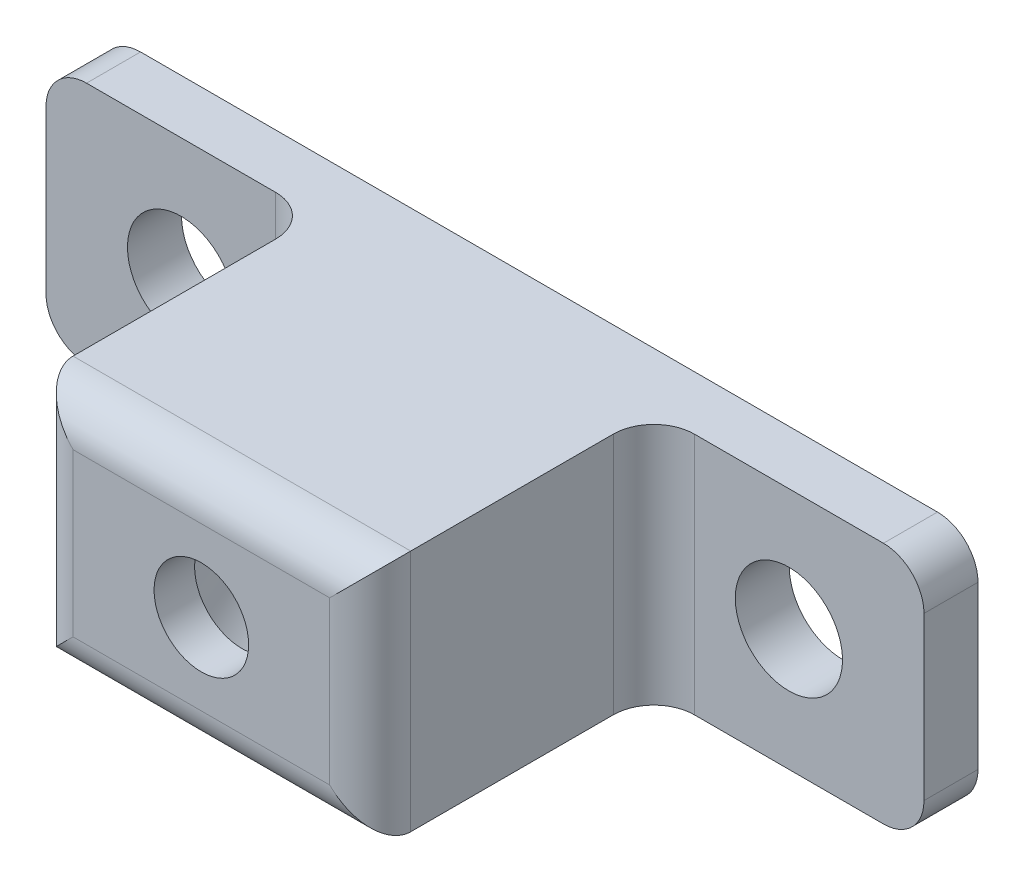
SolidWorks part; units mm, degrees
ref_plane "Front Plane" through (0, 0, 0) normal (0, 0, 1) x (1, 0, 0)
ref_plane "Top Plane" through (0, 0, 0) normal (0, 1, 0) x (1, 0, 0)
ref_plane "Right Plane" through (0, 0, 0) normal (1, 0, 0) x (0, 0, -1)
sketch "Sketch1" plane through (0, 0, 0) normal (0, 0, 1) x (1, 0, 0)
  line L0 (25, 18) -> (0, 0) construction
  line L1 (0, 0) -> (25, 0)
  line L2 (0, 0) -> (0, 18)
  line L3 (0, 18) -> (25, 18)
  line L4 (25, 0) -> (25, 18)
  line L5 (0, 18) -> (25, 0) construction
  circle A0 centre (12.5, 9) radius 3.5
  dimension "D1" = 7
  dimension "D2" = 25
  dimension "D3" = 18
extrude "Boss-Extrude1" add sketch "Sketch1" along normal blind 25
sketch "Sketch2" plane through (0, 0, 0) normal (0, 0, -1) x (-1, 0, 0)
  line L0 (20, 0) -> (0, 18) construction
  line L1 (0, 18) -> (20, 18)
  line L2 (0, 18) -> (0, 0)
  line L3 (0, 0) -> (20, 0)
  line L4 (20, 18) -> (20, 0)
  line L5 (20, 18) -> (0, 0) construction
  line L6 (-25, 0) -> (-45, 18) construction
  line L7 (-25, 0) -> (-45, 0)
  line L8 (-25, 0) -> (-25, 18)
  line L9 (-25, 18) -> (-45, 18)
  line L10 (-45, 0) -> (-45, 18)
  line L12 (-25, 18) -> (-45, 0) construction
  circle A0 centre (10, 9) radius 3.9688
  circle A1 centre (-35, 9) radius 3.9688
  dimension "D1" = 7.9375
  dimension "D2" = 20
extrude "Boss-Extrude2" add sketch "Sketch2" against normal blind 4
fillet "Fillet2" radius 3 6 edges at (-20, 0, 2) (-20, 18, 2) (45, 0, 2) (45, 18, 2)
fillet "Fillet4" radius 3 4 edges at (12.5, 0, 25) (12.5, 18, 25) (0, 9, 25) (25, 9, 25)
sketch "Sketch3" plane through (0, 0, 0) normal (0, 0, -1) x (-1, 0, 0)
  circle A0 centre (-12.5, 9) radius 4.65
extrude "Cut-Extrude1" cut sketch "Sketch3" against normal offset from surface (22 mm away) 3 up to face at (12.5, 9, 25)
sketch "Sketch5" plane through (0, 0, 0) normal (0, 0, -1) x (-1, 0, 0)
  line L1 (-3, 3) -> (-22, 3)
  line L5 (17, 0) -> (-42, 0) construction
  line L6 (-42, 18) -> (17, 18) construction
  line L8 (-3, 3) -> (-3, 15)
  line L9 (-3, 15) -> (-22, 15)
  line L10 (-22, 3) -> (-22, 15)
  line L11 (-25, 18) -> (-25, 0) construction
  line L12 (0, 18) -> (0, 0) construction
  dimension "D2" = 3
  dimension "D3" = 3
  dimension "D4" = 3
  dimension "D5" = 3
extrude "Cut-Extrude2" cut sketch "Sketch5" against normal offset from surface (22 mm away) 3 up to face at (12.5, 9, 25)
chamfer "Chamfer1" distance 1.25 angle 75 2 edges at (12.5, 15, 22) (12.5, 3, 22) first distance on face at (9, 9, 22)
chamfer "Chamfer2" distance 4.5 angle 60 2 edges at (22, 9, 22) (3, 9, 22) first distance on face at (9, 9, 22)
fillet "Fillet5" radius 5.54 4 edges at (6.1533, 3.625, 19.6675) (18.8467, 3.625, 19.6675) (18.8467, 14.375, 19.6675) (6.1533, 14.375, 19.6675)
sketch "Sketch7" plane through (0, 0, 0) normal (0, 0, -1) x (-1, 0, 0)
  line L1 (-11, 0) -> (-14, 0)
  line L2 (-11, 0) -> (-11, 3)
  line L3 (-11, 3) -> (-14, 3)
  line L4 (-14, 0) -> (-14, 3)
  line L5 (-22, 3) -> (-3, 3) construction
  line L6 (17, 0) -> (-42, 0) construction
  point P8 (-12.5, 3)
  point P9 (-12.5, 3)
  dimension "D1" = 3
extrude "Cut-Extrude3" cut sketch "Sketch7" against normal blind 6
equation "\"D2@Sketch5\"=\"D5@Sketch5\""
